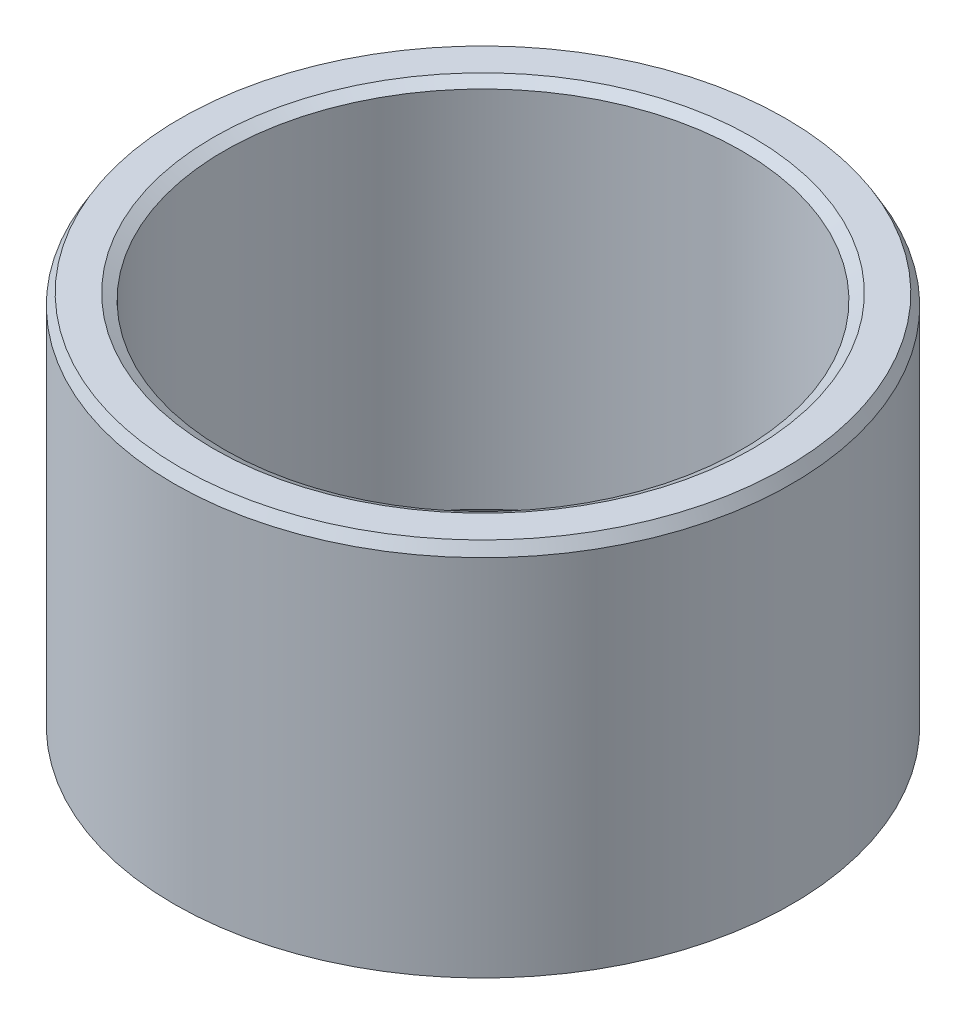
SolidWorks part; units mm, degrees
ref_plane "Front Plane" through (0, 0, 0) normal (0, 0, 1) x (1, 0, 0)
ref_plane "Top Plane" through (0, 0, 0) normal (0, 1, 0) x (1, 0, 0)
ref_plane "Right Plane" through (0, 0, 0) normal (1, 0, 0) x (0, 0, -1)
sketch "Sketch1" plane through (0, 0, 0) normal (0, 1, 0) x (1, 0, 0)
  circle A0 centre (0, 0) radius 37.5
  dimension "SLEEVE_OD" = 75
extrude "Boss-Extrude1" add sketch "Sketch1" along normal blind 46.2879
sketch "Sketch2" plane through (0, 0, 0) normal (0, 1, 0) x (1, 0, 0)
  circle A0 centre (0, 0) radius 31.4223
  dimension "BORE_D" = 62.8446
extrude "Cut-Extrude1" cut sketch "Sketch2" along normal through all
chamfer "Chamfer1" distance 1.323 angle 30 4 edges at (0, 46.2879, 31.4223) (0, 0, 31.4223) (0, 0, 37.5) (0, 46.2879, 37.5) first distance on face at (0, 46.2879, 31.4223) first distance on face at (0, 0, 31.4223) first distance on face at (0, 46.2879, 37.5)
